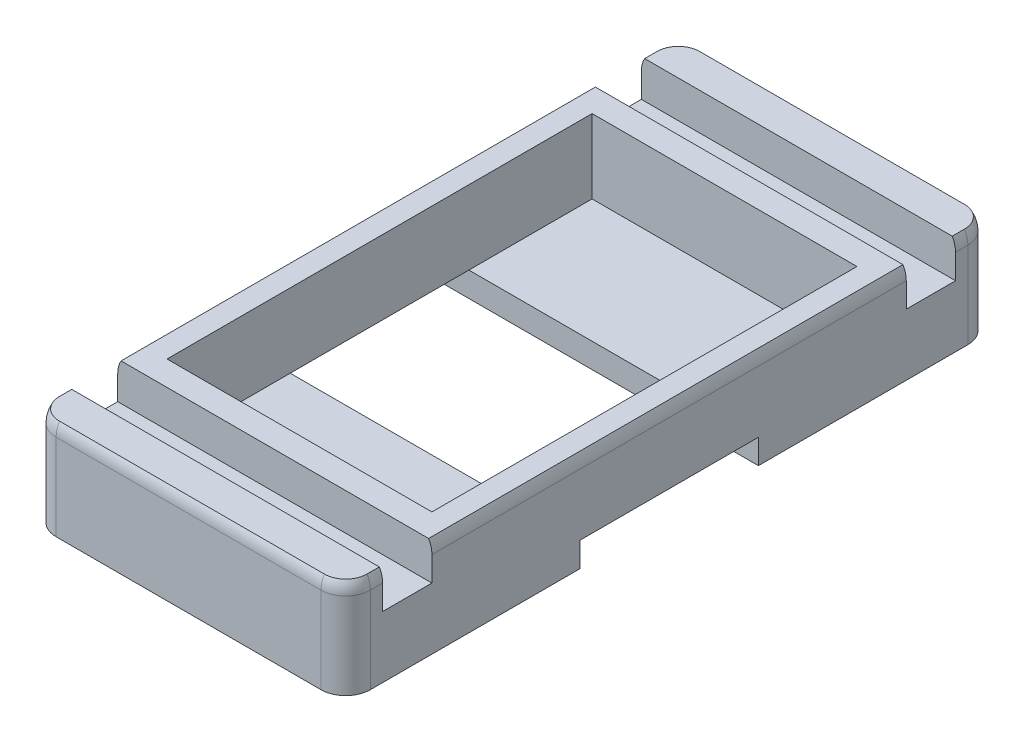
SolidWorks part; units mm, degrees
ref_plane "前视基准面" through (0, 0, 0) normal (0, 0, 1) x (1, 0, 0)
ref_plane "上视基准面" through (0, 0, 0) normal (0, 1, 0) x (1, 0, 0)
ref_plane "右视基准面" through (0, 0, 0) normal (1, 0, 0) x (0, 0, -1)
sketch "草图1" plane through (0, 0, 0) normal (0, 1, 0) x (1, 0, 0)
  line L1 (-13.733, 12.8763) -> (7.767, 12.8763)
  line L2 (-13.733, 12.8763) -> (-13.733, -21.6237)
  line L3 (-13.733, -21.6237) -> (7.767, -21.6237)
  line L4 (7.767, 12.8763) -> (7.767, -21.6237)
  line L5 (-13.733, 21.8763) -> (7.767, 21.8763)
  line L7 (9.767, 19.8763) -> (9.767, -28.6237)
  line L9 (7.767, -30.6237) -> (-13.733, -30.6237)
  line L11 (-15.733, -28.6237) -> (-15.733, 19.8763)
  arc A0 (7.767, 21.8763) -> (9.767, 19.8763) centre (7.767, 19.8763) cw
  arc A1 (9.767, -28.6237) -> (7.767, -30.6237) centre (7.767, -28.6237) cw
  arc A2 (-15.733, -28.6237) -> (-13.733, -30.6237) centre (-13.733, -28.6237) ccw
  arc A3 (-13.733, 21.8763) -> (-15.733, 19.8763) centre (-13.733, 19.8763) ccw
extrude "凸台-拉伸2" add sketch "草图1" along normal blind 11
fillet "圆角1" radius 2 8 edges at (-15.1472, 11, -21.2905) (9.1812, 11, -21.2905) (-2.983, 11, -21.8763) (9.767, 11, 4.3737) (9.1812, 11, 30.0379) (-15.1472, 11, 30.0379) (-2.983, 11, 30.6237) (-15.733, 11, 4.3737)
sketch "草图2" plane through (0, 11, 0) normal (0, 1, 0) x (1, 0, 0)
  line L1 (-22.0435, 24.7429) -> (17.13, 24.7429)
  line L2 (-22.0435, 24.7429) -> (-22.0435, -33.1144)
  line L3 (-22.0435, -33.1144) -> (17.13, -33.1144)
  line L4 (17.13, 24.7429) -> (17.13, -33.1144)
extrude "切除-拉伸1" cut sketch "草图2" against normal blind 1
sketch "草图3" plane through (0, 0, 0) normal (0, -1, 0) x (-1, 0, 0)
  line L0 (-7.767, -21.6237) -> (-7.767, 12.8763) construction
  line L1 (13.733, -21.6237) -> (-7.767, -21.6237)
  line L2 (13.733, -21.6237) -> (13.733, -11.6237)
  line L3 (13.733, -11.6237) -> (-7.767, -11.6237)
  line L4 (-7.767, -21.6237) -> (-7.767, -11.6237)
  line L5 (-7.767, 12.8763) -> (13.733, 12.8763) construction
  line L6 (13.733, 12.8763) -> (-7.767, 12.8763)
  line L7 (13.733, 12.8763) -> (13.733, 2.8763)
  line L8 (13.733, 2.8763) -> (-7.767, 2.8763)
  line L9 (-7.767, 12.8763) -> (-7.767, 2.8763)
extrude "凸台-拉伸3" add sketch "草图3" against normal blind 3
sketch "草图4" plane through (0, 10, 0) normal (0, 1, 0) x (1, 0, 0)
  line L1 (-20.4033, 24.2821) -> (16.1738, 24.2821)
  line L2 (-20.4033, 24.2821) -> (-20.4033, -36.205)
  line L3 (-20.4033, -36.205) -> (16.1738, -36.205)
  line L4 (16.1738, 24.2821) -> (16.1738, -36.205)
extrude "切除-拉伸2" cut sketch "草图4" against normal blind 1
sketch "草图5" plane through (-13.733, 0, 0) normal (1, 0, 0) x (0, 0, -1)
  line L0 (2.8763, 0) -> (-11.6237, 0) construction
  line L1 (-11.6237, 3) -> (2.8763, 3)
  line L2 (-11.6237, 3) -> (-11.6237, 0)
  line L3 (-11.6237, 0) -> (2.8763, 0)
  line L4 (2.8763, 3) -> (2.8763, 0)
extrude "切除-拉伸3" cut sketch "草图5" against normal blind 11
sketch "草图6" plane through (7.767, 0, 0) normal (-1, 0, 0) x (0, 0, 1)
  line L0 (11.6237, 0) -> (-2.8763, 0) construction
  line L1 (-2.8763, 3) -> (11.6237, 3)
  line L2 (-2.8763, 3) -> (-2.8763, 0)
  line L3 (-2.8763, 0) -> (11.6237, 0)
  line L4 (11.6237, 3) -> (11.6237, 0)
extrude "切除-拉伸4" cut sketch "草图6" against normal blind 11
sketch "草图7" plane through (0, 0, 0) normal (0, -1, 0) x (-1, 0, 0)
  line L1 (-24.2644, 23.6739) -> (33.2575, 23.6739)
  line L2 (-24.2644, 23.6739) -> (-24.2644, -36.3132)
  line L3 (-24.2644, -36.3132) -> (33.2575, -36.3132)
  line L4 (33.2575, 23.6739) -> (33.2575, -36.3132)
extrude "切除-拉伸5" cut sketch "草图7" against normal blind 1
sketch "草图8" plane through (0, 9, 0) normal (0, 1, 0) x (1, 0, 0)
  line L0 (-13.733, 21.8763) -> (7.767, 21.8763)
  line L1 (9.767, 19.8763) -> (9.767, -28.6237)
  line L2 (-13.733, -30.6237) -> (7.767, -30.6237)
  line L3 (-15.733, 19.8763) -> (-15.733, -28.6237)
  line L5 (-13.733, 12.8763) -> (7.767, 12.8763)
  line L6 (-13.733, 12.8763) -> (-13.733, -21.6237)
  line L7 (-13.733, -21.6237) -> (7.767, -21.6237)
  line L8 (7.767, 12.8763) -> (7.767, -21.6237)
  arc A0 (-15.733, -28.6237) -> (-13.733, -30.6237) centre (-13.733, -28.6237) ccw
  arc A1 (-15.733, -28.6237) -> (-13.733, -30.6237) centre (-13.733, -28.6237) ccw construction
  arc A2 (7.767, -30.6237) -> (9.767, -28.6237) centre (7.767, -28.6237) ccw
  arc A3 (7.767, -30.6237) -> (9.767, -28.6237) centre (7.767, -28.6237) ccw construction
  arc A4 (9.767, 19.8763) -> (7.767, 21.8763) centre (7.767, 19.8763) ccw
  arc A5 (9.767, 19.8763) -> (7.767, 21.8763) centre (7.767, 19.8763) ccw construction
  arc A6 (-13.733, 21.8763) -> (-15.733, 19.8763) centre (-13.733, 19.8763) ccw
  arc A7 (-13.733, 21.8763) -> (-15.733, 19.8763) centre (-13.733, 19.8763) ccw construction
  line M1 (-13.733, -21.6237) -> (-13.733, 12.8763)
  line M2 (-13.733, 12.8763) -> (7.767, 12.8763)
  line M3 (7.767, 12.8763) -> (7.767, -21.6237)
  line M4 (7.767, -21.6237) -> (-13.733, -21.6237)
  arc M5 (9.767, 19.8763) -> (7.767, 21.8763) centre (7.767, 19.8763) ccw
  line M6 (7.767, 21.8763) -> (-13.733, 21.8763)
  arc M7 (-13.733, 21.8763) -> (-15.733, 19.8763) centre (-13.733, 19.8763) ccw
  line M8 (-15.733, 19.8763) -> (-15.733, -28.6237)
  arc M9 (-15.733, -28.6237) -> (-13.733, -30.6237) centre (-13.733, -28.6237) ccw
  line M10 (-13.733, -30.6237) -> (7.767, -30.6237)
  arc M11 (7.767, -30.6237) -> (9.767, -28.6237) centre (7.767, -28.6237) ccw
  line M12 (9.767, -28.6237) -> (9.767, 19.8763)
extrude "凸台-拉伸4" add sketch "草图8" along normal blind 1 contours M12 M5 M6 M7 M8 M9 M10 M11 M4 M1 M2 M3 region at (-2.983, 9, -21.2926)
fillet "圆角2" radius 2 8 edges at (9.1812, 10, 30.0379) (-15.1472, 10, 30.0379) (-2.983, 10, 30.6237) (9.767, 10, 4.3737) (9.1812, 10, -21.2905) (-15.733, 10, 4.3737) (-15.1472, 10, -21.2905) (-2.983, 10, -21.8763)
sketch "草图9" plane through (0, 10, 0) normal (0, 1, 0) x (1, 0, 0)
  line L1 (-19.9122, 25.8024) -> (22.3135, 25.8024)
  line L2 (-19.9122, 25.8024) -> (-19.9122, -33.253)
  line L3 (-19.9122, -33.253) -> (22.3135, -33.253)
  line L4 (22.3135, 25.8024) -> (22.3135, -33.253)
extrude "切除-拉伸6" cut sketch "草图9" against normal blind 1
sketch "草图10" plane through (-15.733, 0, 0) normal (-1, 0, 0) x (0, 0, 1)
  line L0 (-19.8763, 8) -> (-12.8763, 8)
  line L1 (28.6237, 8) -> (-19.8763, 8) construction
  line L2 (-14.8763, 8) -> (-14.8763, 6)
  line L3 (-14.8763, 6) -> (-18.8763, 6)
  line L4 (-14.8763, 11.795) -> (-14.8763, 8)
  line L5 (-18.8763, 6) -> (-18.8763, 11.795)
  line L6 (-18.8763, 11.795) -> (-14.8763, 11.795)
extrude "切除-拉伸8" cut sketch "草图10" against normal blind 30 contours L5 L3 L2 L0 | L6 L5 L0 L4 region at (-15.733, 9.8975, -16.8763) region at (-15.733, 7, -16.8763)
sketch "草图11" plane through (-15.733, 0, 0) normal (-1, 0, 0) x (0, 0, 1)
  line L1 (28.6237, 8) -> (-14.8763, 8) construction
  line L2 (23.6237, 8) -> (23.6237, 14.2339)
  line L3 (23.6237, 14.2339) -> (27.6237, 14.2339)
  line L4 (27.6237, 14.2339) -> (27.6237, 8)
  line L5 (27.6237, 8) -> (27.6237, 6)
  line L6 (27.6237, 6) -> (23.6237, 6)
  line L7 (23.6237, 6) -> (23.6237, 8)
extrude "切除-拉伸9" cut sketch "草图11" against normal blind 30
